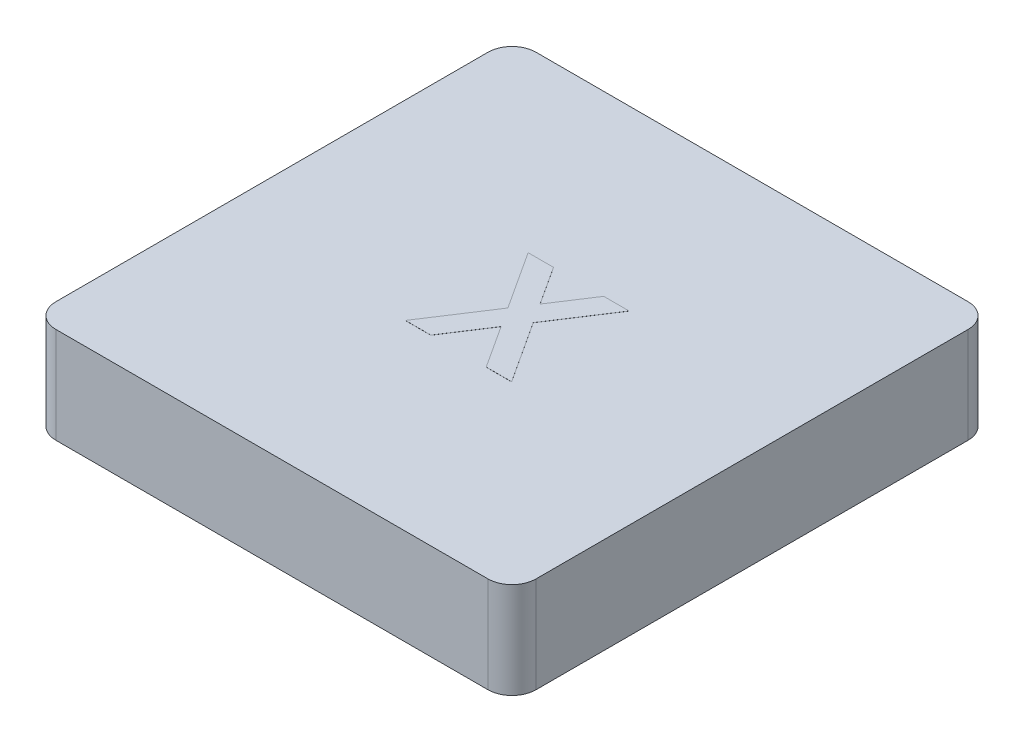
SolidWorks part; units mm, degrees
ref_plane "Front Plane" through (0, 0, 0) normal (0, 0, 1) x (1, 0, 0)
ref_plane "Top Plane" through (0, 0, 0) normal (0, 1, 0) x (1, 0, 0)
ref_plane "Right Plane" through (0, 0, 0) normal (1, 0, 0) x (0, 0, -1)
sketch "Sketch1" plane through (0, 0, 0) normal (0, 1, 0) x (1, 0, 0)
  line L0 (0, 0) -> (12.7, 0)
  line L1 (12.7, 0) -> (12.7, 12.7)
  line L2 (12.7, 12.7) -> (0, 12.7)
  line L3 (0, 12.7) -> (0, 0)
  dimension "D1" = 12.7
  dimension "D2" = 12.7
extrude "Boss-Extrude1" add sketch "Sketch1" along normal blind 2.54
fillet "Fillet1" radius 0.635 4 edges at (0, 1.27, -12.7) (12.7, 1.27, -12.7) (12.7, 1.27, 0) (0, 1.27, 0)
shell "Shell1" thickness 0.635 removed face at (6.35, 0, -6.35)
sketch "Sketch2" plane through (0, 1.905, 0) normal (0, -1, 0) x (-1, 0, 0)
  line L0 (-0.635, 6.35) -> (-12.065, 6.35) construction
  line L1 (-0.635, 12.065) -> (-0.635, 0.635) construction
  line L2 (-12.065, 0.635) -> (-12.065, 12.065) construction
  line L3 (-6.35, 0.635) -> (-6.35, 12.065) construction
  line L4 (-0.635, 0.635) -> (-12.065, 0.635) construction
  line L5 (-12.065, 12.065) -> (-0.635, 12.065) construction
  circle A0 centre (-6.35, 6.35) radius 2.54
  dimension "D1" = 5.08
extrude "Boss-Extrude2" add sketch "Sketch2" along normal up to surface (1.905 mm away) up to face at (6.35, 0, -6.35)
sketch "Sketch3" plane through (0, 2.54, 0) normal (0, 1, 0) x (1, 0, 0)
  line L0 (0, 12.065) -> (0, 0.635) construction
  line L1 (0.635, 0) -> (12.065, 0) construction
  text T0 "<b>X</b>"
  point P1 (0, 0)
  dimension "D1" = 4.953
  dimension "D2" = 4.826
extrude "Boss-Extrude3" add sketch "Sketch3" along normal blind 0.0025
